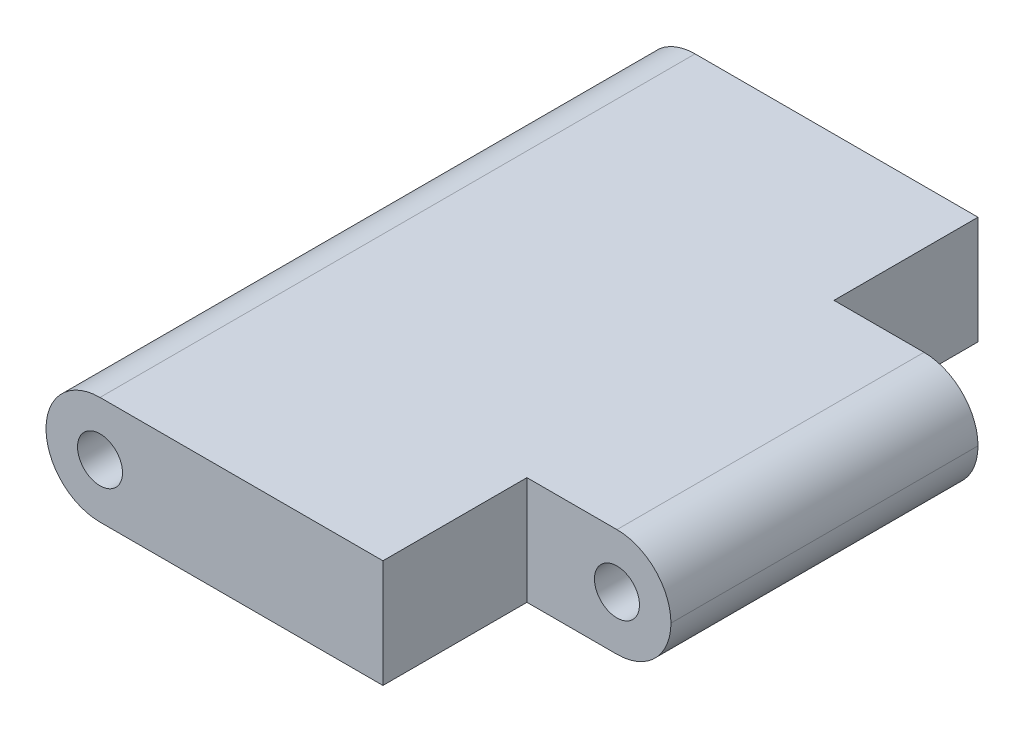
SolidWorks part; units mm, degrees
ref_plane "Front Plane" through (0, 0, 0) normal (0, 0, 1) x (1, 0, 0)
ref_plane "Top Plane" through (0, 0, 0) normal (0, 1, 0) x (1, 0, 0)
ref_plane "Right Plane" through (0, 0, 0) normal (1, 0, 0) x (0, 0, -1)
sketch "Sketch1" plane through (0, 0, 0) normal (0, 1, 0) x (1, 0, 0)
  line L0 (0, 0) -> (0, 16.529)
  line L1 (0, 16.529) -> (13.3591, 16.529)
  line L2 (13.3591, 16.529) -> (13.3591, 0)
  line L3 (13.3591, 0) -> (0, 0)
extrude "Boss-Extrude1" add sketch "Sketch1" along normal blind 3
sketch "Sketch2" plane through (0, 3, 0) normal (0, 1, 0) x (1, 0, 0)
  line L3 (13.3591, 16.529) -> (0, 16.529) construction
  line L6 (9.3591, 16.529) -> (9.3591, 12.529)
  line L7 (9.3591, 12.529) -> (13.3591, 12.529)
  line L8 (13.3591, 0) -> (13.3591, 16.529) construction
  line L9 (13.3591, 12.529) -> (13.3591, 16.529)
  line L10 (13.3591, 16.529) -> (9.3591, 16.529)
  line L13 (0, 0) -> (13.3591, 0) construction
  line L16 (13.3591, 4) -> (9.3591, 4)
  line L17 (9.3591, 4) -> (9.3591, 0)
  line L18 (9.3591, 0) -> (13.3591, 0)
  line L19 (13.3591, 0) -> (13.3591, 4)
  dimension "D1" = 4
  dimension "D2" = 4
  dimension "D3" = 4
  dimension "D4" = 4
extrude "Cut-Extrude1" cut sketch "Sketch2" against normal through all
fillet "Fillet1" radius 1.5 4 edges at (13.3591, 0, -8.2645) (13.3591, 3, -8.2645) (0, 0, -8.2645) (0, 3, -8.2645)
sketch "Sketch5" plane through (0, 0, 0) normal (0, 0, 1) x (1, 0, 0)
  line L0 (1.5, 3) -> (1.5, 0) construction
  line L1 (11.8591, 3) -> (11.8591, 0) construction
  arc A0 (13.3591, 1.5) -> (11.8591, 3) centre (11.8591, 1.5) ccw construction
  circle A1 centre (1.5, 1.5) radius 0.625
  circle A2 centre (11.8591, 1.5) radius 0.625
  dimension "D1" = 1.25
  dimension "D2" = 1.25
extrude "Cut-Extrude3" cut sketch "Sketch5" against normal through all
